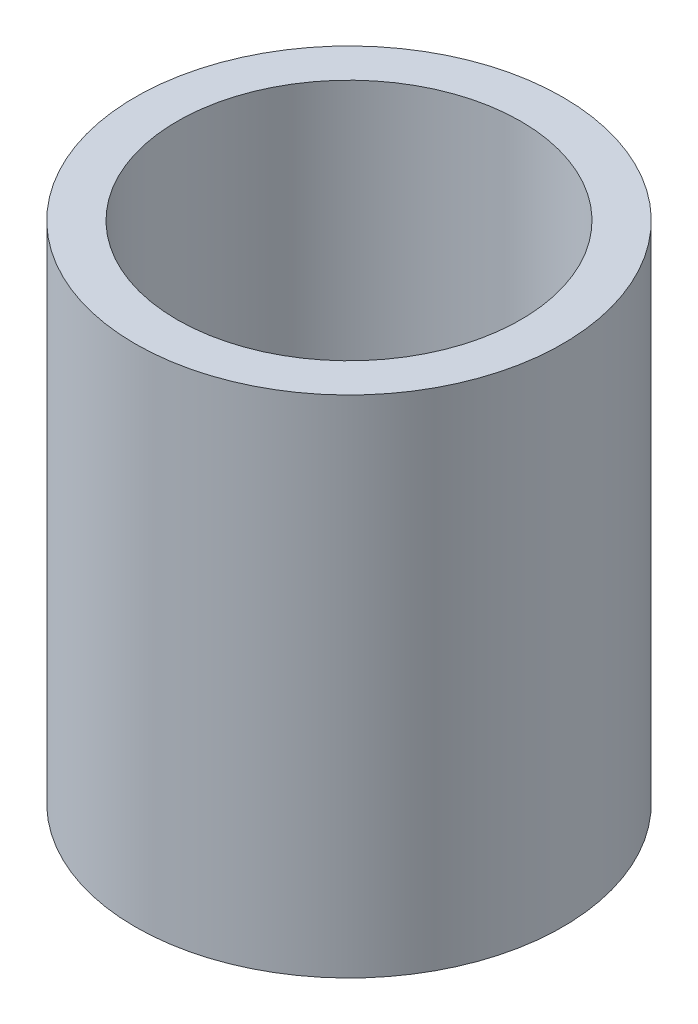
SolidWorks part; units mm, degrees
ref_plane "Front Plane" through (0, 0, 0) normal (0, 0, 1) x (1, 0, 0)
ref_plane "Top Plane" through (0, 0, 0) normal (0, 1, 0) x (1, 0, 0)
ref_plane "Right Plane" through (0, 0, 0) normal (1, 0, 0) x (0, 0, -1)
sketch "Sketch1" plane through (0, 70.8213, 0) normal (0, -1, 0) x (1, 0, 0)
  circle A0 centre (0, 0) radius 5.1054
  circle A1 centre (0, 0) radius 6.35
  dimension "D1" = 12.7
  dimension "D2" = 10.2108
extrude "Boss-Extrude1" add sketch "Sketch1" along normal blind 15
